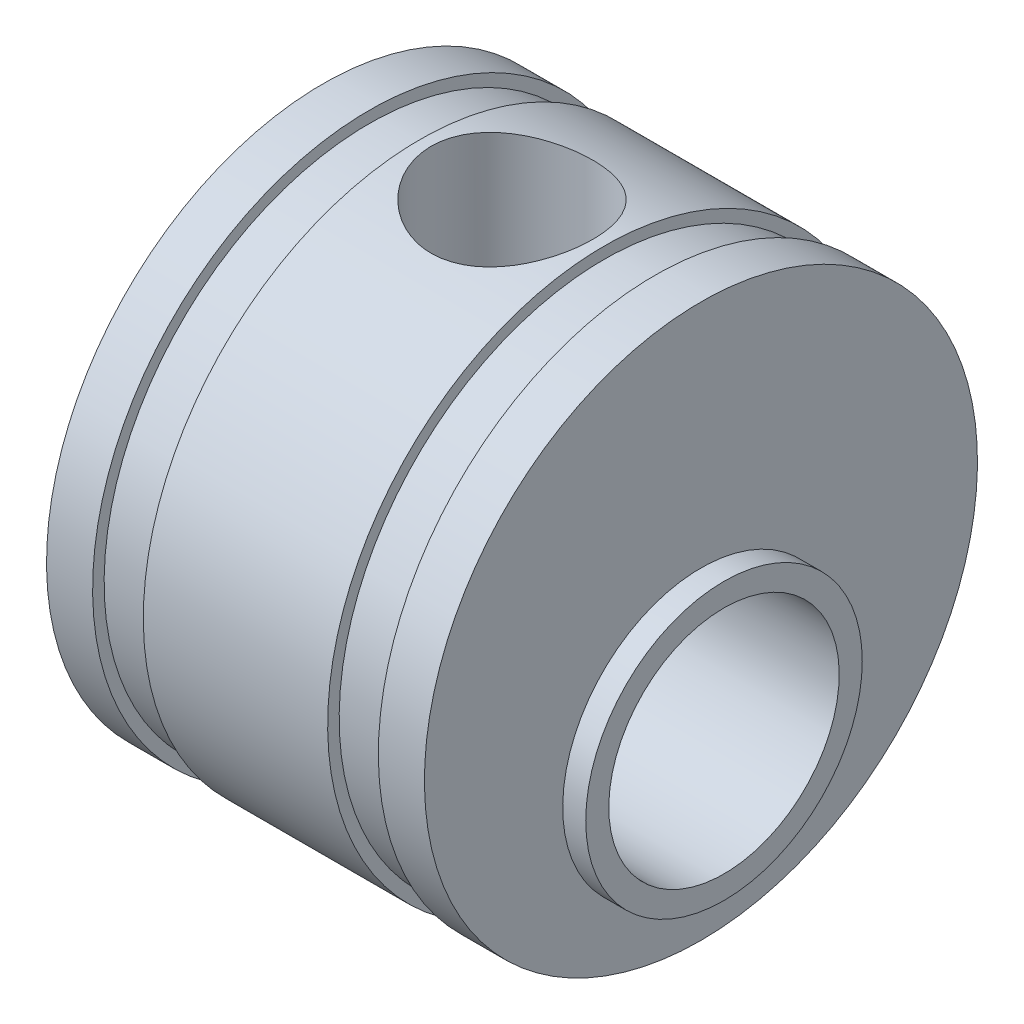
SolidWorks part; units mm, degrees
ref_plane "Front Plane" through (0, 0, 0) normal (0, 0, 1) x (1, 0, 0)
ref_plane "Top Plane" through (0, 0, 0) normal (0, 1, 0) x (1, 0, 0)
ref_plane "Right Plane" through (0, 0, 0) normal (1, 0, 0) x (0, 0, -1)
sketch "Sketch3" plane through (0, 0, 0) normal (0, 0, 1) x (1, 0, 0)
  line L0 (0, 0) -> (8.2, 0) construction
  line L1 (0, 0) -> (0, 6)
  line L2 (0, 6) -> (1, 6)
  line L3 (1, 6) -> (1, 5.75)
  line L4 (1, 5.75) -> (2.1, 5.75)
  line L5 (2.1, 5.75) -> (2.1, 6)
  line L6 (2.1, 6) -> (6.1, 6)
  line L7 (6.1, 6) -> (6.1, 5.75)
  line L8 (6.1, 5.75) -> (7.2, 5.75)
  line L9 (7.2, 5.75) -> (7.2, 6)
  line L10 (7.2, 6) -> (8.2, 6)
  line L11 (8.2, 6) -> (8.2, 0)
  line L12 (0, 0) -> (8.2, 0)
  dimension "D1" = 1
  dimension "D2" = 1.1
  dimension "D3" = 4
  dimension "D4" = 6
  dimension "D5" = 5.75
revolve "Revolve1" add sketch "Sketch3" angle 360 about L0
sketch "Sketch4" plane through (8.2, 0, 0) normal (1, 0, 0) x (0, 0, -1)
  circle A0 centre (0, -2) radius 2.5
  dimension "D1" = 5
  dimension "D2" = 2
extrude "Cut-Extrude1" cut sketch "Sketch4" against normal up to next
ref_plane "Plane1" through (0, 6, 0) normal (0, 1, 0) x (1, 0, 0)
sketch "Sketch5" plane through (0, 6, 0) normal (0, 1, 0) x (1, 0, 0)
  line L0 (2.1, 0) -> (4.1, 0) construction
  line L1 (2.1, 5.75) -> (2.1, -5.75) construction
  line L2 (4.1, 0) -> (6.1, 0) construction
  line L3 (6.1, -6) -> (6.1, 6) construction
  circle A0 centre (4.1, 0) radius 1.7526
  dimension "D1" = 3.5052
extrude "Cut-Extrude2" cut sketch "Sketch5" against normal up to next
sketch "Sketch6" plane through (8.2, 0, 0) normal (1, 0, 0) x (0, 0, -1)
  circle A0 centre (0, -2) radius 3
  circle A1 centre (0, -2) radius 2.5 construction
  circle A2 centre (0, -2) radius 2.5
  dimension "D1" = 6
extrude "Boss-Extrude1" add sketch "Sketch6" along normal blind 0.5
